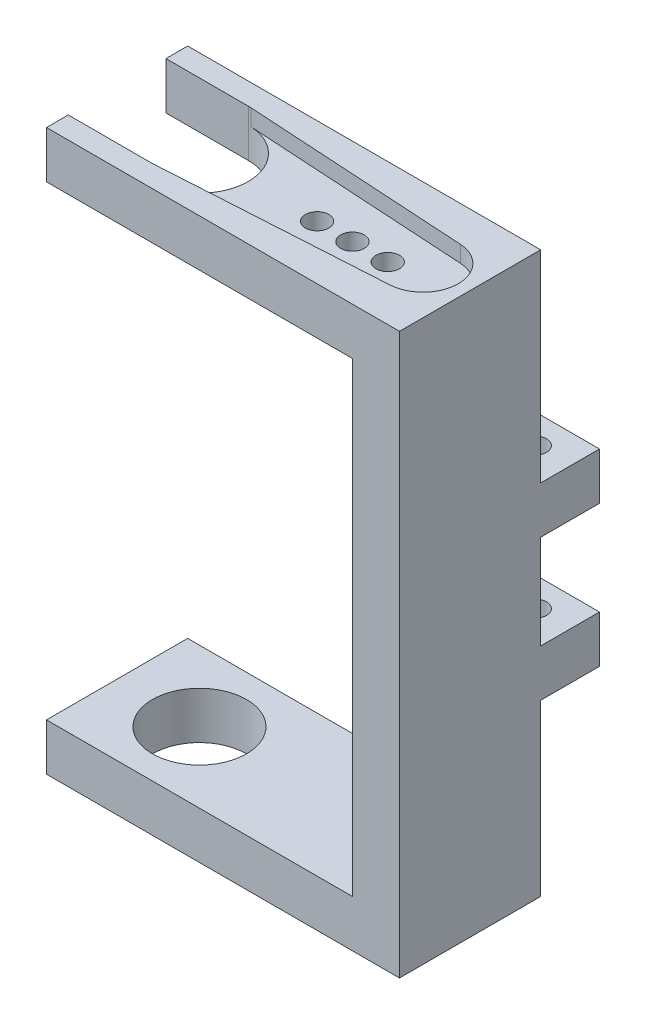
SolidWorks part; units mm, degrees
note: The reader was unsure of these and kept them because the rebuilt part matched: shared geometry of "草图4<3>", "草图5<2>".
ref_plane "前视基准面" through (0, 0, 0) normal (0, 0, 1) x (1, 0, 0)
ref_plane "上视基准面" through (0, 0, 0) normal (0, 1, 0) x (1, 0, 0)
ref_plane "右视基准面" through (0, 0, 0) normal (1, 0, 0) x (0, 0, -1)
other "Configuration Table"
sketch "草图1" plane through (0, 0, 0) normal (0, 0, 1) x (1, 0, 0)
  line L0 (0, 0) -> (26, 0)
  line L1 (26, 0) -> (26, 39.6)
  line L2 (26, 39.6) -> (0, 39.6)
  line L3 (0, 39.6) -> (0, 0) construction
  line L4 (0, -4) -> (30, -4)
  line L5 (30, -4) -> (30, 43.6)
  line L6 (30, 43.6) -> (0, 43.6)
  line L7 (0, 43.6) -> (0, 39.6)
  line L8 (0, 0) -> (0, -4)
  dimension "D1" = 26
  dimension "D2" = 39.6
  dimension "D3" = 4
extrude "凸台-拉伸1" add sketch "草图1" along normal blind 12
sketch "草图2" plane through (0, -4, 0) normal (0, -1, 0) x (1, 0, 0)
  line L0 (0, 6) -> (7, 6) construction
  line L1 (0, 12) -> (0, 0) construction
  circle A0 centre (7, 6) radius 4
  dimension "D1" = 8
  dimension "D2" = 7
extrude "切除-拉伸1" cut sketch "草图2" against normal blind 4
sketch "草图3" plane through (0, 43.6, 0) normal (0, 1, 0) x (1, 0, 0)
  line L0 (0, -6) -> (7, -6) construction
  line L1 (0, -12) -> (0, 0) construction
  line L2 (7, -1.85) -> (0, -1.85)
  line L3 (0, -1.85) -> (0, -10.15)
  line L4 (7, -10.15) -> (0, -10.15)
  circle A0 centre (7, -6) radius 4.15
  dimension "D1" = 8.3
  dimension "D2" = 7
extrude "切除-拉伸2" cut sketch "草图3" against normal blind 4
sketch "草图4" plane through (0, 43.6, 0) normal (0, 1, 0) x (1, 0, 0)
  line L0 (7, -6) -> (26, -6) construction
  line L1 (7.2512, -1.8576) -> (26.1816, -3.0055)
  line L2 (7.2512, -10.1424) -> (26.1816, -8.9945)
  circle A0 centre (26, -6) radius 1
  circle A1 centre (23, -6) radius 1
  circle A2 centre (20, -6) radius 1
  circle A3 centre (17, -6) radius 1
  circle A4 centre (26, -6) radius 3
  arc A5 (7, -10.15) -> (7, -1.85) centre (7, -6) ccw construction
  arc A6 (7, -10.15) -> (7, -1.85) centre (7, -6) ccw
  dimension "D5" = 2
  dimension "D6" = 2
  dimension "D7" = 2
  dimension "D8" = 2
  dimension "D9" = 6
  dimension "D1" = 19
  dimension "D2" = 10
  dimension "D3" = 3
  dimension "D4" = 3
extrude "切除-拉伸3" cut sketch "草图4" against normal blind 1.4
extrude "切除-拉伸4" cut sketch "草图4<3>" against normal blind 4 contours A4 L0 A1 | L0 A4 A1 | L0 A1 A4 | A1 L0 A4 | A2 L0 | L0 A2 | A3 L0 | L0 A3
sketch "草图4<3>" plane through (0, 43.6, 0) normal (0, 1, 0) x (1, 0, 0) same geometry as "草图4"
ref_plane "基准面1" through (0, 16.44, 0) normal (0, 1, 0) x (1, 0, 0)
sketch "草图5" plane through (0, 16.44, 0) normal (0, 1, 0) x (1, 0, 0)
  line L0 (30, 0) -> (30, 5)
  line L1 (30, 5) -> (24, 5)
  line L2 (24, 5) -> (24, 0)
  line L3 (30, 0) -> (0, 0) construction
  line L4 (24, 0) -> (30, 0)
  line L5 (24, 2.5) -> (30, 2.5) construction
  circle A0 centre (27, 2.5) radius 1
  dimension "D1" = 2
  dimension "D2" = 5
  dimension "D3" = 6
extrude "凸台-拉伸2" add sketch "草图5" along normal blind 4 from offset 6
extrude "凸台-拉伸3" add sketch "草图5<2>" along normal blind 4 from offset 6 offset against normal yes
sketch "草图5<2>" plane through (0, 16.44, 0) normal (0, 1, 0) x (1, 0, 0) same geometry as "草图5"
fillet "圆角1" radius 2 2 edges at (26, 12.44, 0) (26, 24.44, 0)
ref_plane "基准面2" through (-10, 0, 0) normal (1, 0, 0) x (0, 0, -1)
